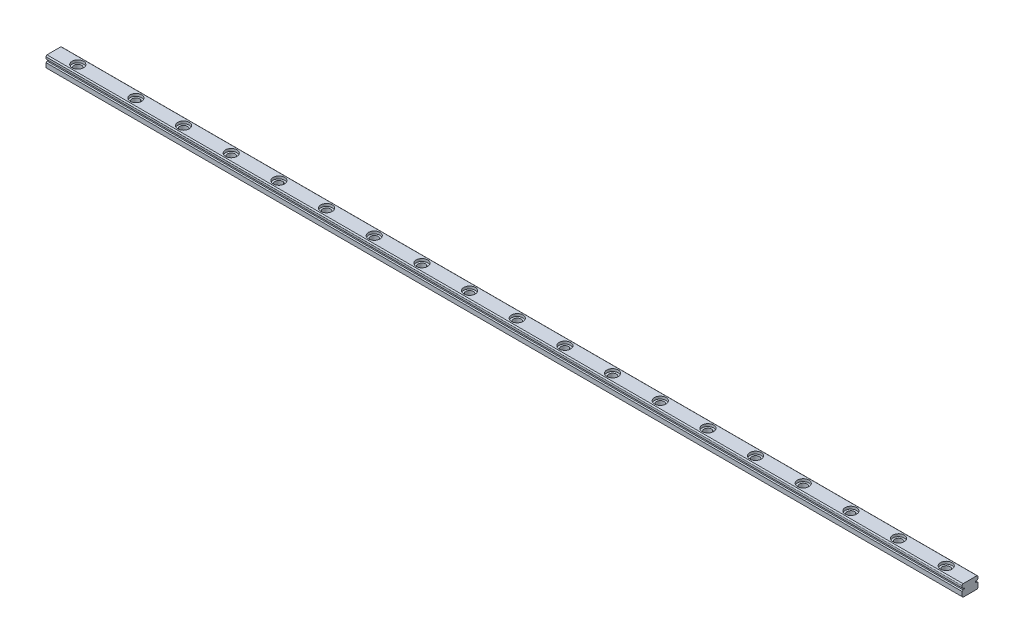
SolidWorks part; units mm, degrees
ref_plane "Front Plane" through (0, 0, 0) normal (0, 0, 1) x (1, 0, 0)
ref_plane "Top Plane" through (0, 0, 0) normal (0, 1, 0) x (1, 0, 0)
ref_plane "Right Plane" through (0, 0, 0) normal (1, 0, 0) x (0, 0, -1)
sketch "Sketch1" plane through (0, 0, 0) normal (1, 0, 0) x (0, 0, -1)
  line L0 (-2.5, 0.3) -> (-2.2, 0)
  line L1 (-2.2, 0) -> (2.2, 0)
  line L2 (2.2, 0) -> (2.5, 0.3)
  line L3 (2.5, 0.3) -> (2.5, 1.723)
  line L4 (2.1917, 2) -> (1.85, 2)
  line L5 (1.75, 2.1) -> (1.75, 2.3)
  line L6 (1.85, 2.4) -> (2.1917, 2.4)
  line L7 (2.5, 2.677) -> (2.5, 3.3)
  line L8 (2.2, 3.7) -> (-2.2, 3.7)
  line L9 (-2.5, 3.3) -> (-2.5, 2.677)
  line L10 (-2.1917, 2.4) -> (-1.85, 2.4)
  line L11 (-1.75, 2.3) -> (-1.75, 2.1)
  line L12 (-1.85, 2) -> (-2.1917, 2)
  line L13 (-2.5, 1.723) -> (-2.5, 0.3)
  arc A0 (2.5, 1.723) -> (2.1917, 2) centre (2.65, 2.2) cw
  arc A1 (1.85, 2) -> (1.75, 2.1) centre (1.85, 2.1) cw
  arc A2 (1.75, 2.3) -> (1.85, 2.4) centre (1.85, 2.3) cw
  arc A3 (2.1917, 2.4) -> (2.5, 2.677) centre (2.65, 2.2) cw
  arc A4 (2.5, 3.3) -> (2.2, 3.7) centre (1.9137, 3.1727) ccw
  arc A5 (-2.2, 3.7) -> (-2.5, 3.3) centre (-1.9137, 3.1727) ccw
  arc A6 (-2.5, 2.677) -> (-2.1917, 2.4) centre (-2.65, 2.2) cw
  arc A7 (-1.85, 2.4) -> (-1.75, 2.3) centre (-1.85, 2.3) cw
  arc A8 (-1.75, 2.1) -> (-1.85, 2) centre (-1.85, 2.1) cw
  arc A9 (-2.1917, 2) -> (-2.5, 1.723) centre (-2.65, 2.2) cw
extrude "Extrude1" add sketch "Sketch1" along normal blind 288.29
sketch "Sketch2" plane through (0, 0, 0) normal (0, 0, -1) x (-1, 0, 0)
  line L0 (-7.5, 3.7) -> (-5.7, 3.7)
  line L1 (-5.7, 3.7) -> (-5.7, 2.9)
  line L2 (-5.7, 2.9) -> (-6.3, 2.9)
  line L3 (-6.3, 2.9) -> (-6.3, 0.2)
  line L4 (-6.3, 0.2) -> (-6.1, 0)
  line L5 (-6.1, 0) -> (-7.5, 0)
  line L6 (0, 1.723) -> (0, 0.3) construction
  line L7 (-7.5, 0) -> (-7.5, 3.7) construction
  line L8 (-7.5, 3.7) -> (-7.5, 0)
  line L9 (-288.29, 0) -> (0, 0) construction
  line L10 (-288.29, 3.7) -> (0, 3.7) construction
  dimension "D1" = 7.5
  dimension "D2" = 2.4
  dimension "D3" = 2.8
  dimension "D4" = 45
  dimension "D5" = 3.6
  dimension "D6" = 0.8
revolve "Cut-Revolve1" cut sketch "Sketch2" angle 360 about L7 reverse direction yes
sketch "Sketch3" plane through (45, 0, 0) normal (0, 0, -1) x (-1, 0, 0)
  line L0 (-235.79, 3.7) -> (-233.99, 3.7)
  line L1 (-233.99, 3.7) -> (-233.99, 2.9)
  line L2 (-233.99, 2.9) -> (-234.59, 2.9)
  line L3 (-234.59, 2.9) -> (-234.59, 0.2)
  line L4 (-234.59, 0.2) -> (-234.39, 0)
  line L5 (-234.39, 0) -> (-235.79, 0)
  line L6 (-243.29, 1.723) -> (-243.29, 0.3) construction
  line L7 (-235.79, 0) -> (-235.79, 3.7) construction
  line L8 (-243.29, 3.7) -> (45, 3.7) construction
  line L9 (-243.29, 0) -> (45, 0) construction
  line L10 (-235.79, 3.7) -> (-235.79, 0)
  dimension "D1" = 7.5
  dimension "D2" = 2.4
  dimension "D3" = 2.8
  dimension "D4" = 3.6
  dimension "D5" = 0.8
  dimension "D6" = 45
revolve "Cut-Revolve2" cut sketch "Sketch3" angle 360 about L7 reverse direction yes
ref_axis "Axis1" through (-3, 0, 0) along (1, 0, 0)
pattern_linear "LPattern1" count 18 spacing 15 along (-1, 0, 0) of "Cut-Revolve2"
